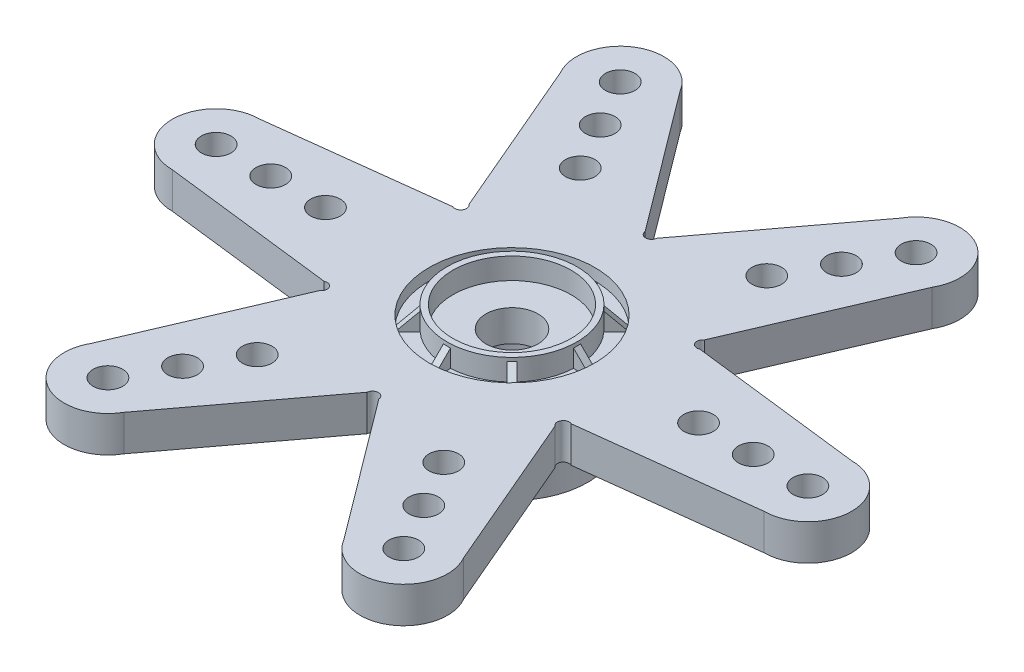
SolidWorks part; units mm, degrees
ref_plane "Front Plane" through (0, 0, 0) normal (0, 0, 1) x (1, 0, 0)
ref_plane "Top Plane" through (0, 0, 0) normal (0, 1, 0) x (1, 0, 0)
ref_plane "Right Plane" through (0, 0, 0) normal (1, 0, 0) x (0, 0, -1)
sketch "Sketch1" plane through (0, 0, 0) normal (0, 1, 0) x (1, 0, 0)
  line L0 (5.7752, -3.8298) -> (0, 0)
  line L1 (6.3503, 3.495) -> (6.3503, 3.8298)
  line L2 (6.3497, -3.4899) -> (15.8747, -2.3469)
  line L3 (6.3503, 3.495) -> (15.8747, 2.3521)
  line L4 (5.7752, 3.8298) -> (0, 0)
  line L5 (6.3503, 3.8298) -> (5.7752, 3.8298)
  line L6 (6.3497, -3.4899) -> (6.3497, -3.8298)
  line L7 (6.3497, -3.8298) -> (5.7752, -3.8298)
  arc A0 (15.8747, -2.3469) -> (15.8747, 2.3521) centre (15.8747, 0.0026) ccw
  dimension "D2" = 4.699
extrude "Extrude4" add sketch "Sketch1" along normal blind 1.9304
sketch "Sketch2" plane through (0, 1.9304, 0) normal (0, 1, 0) x (-1, 0, 0)
  circle A0 centre (-6.3426, -4.1499) radius 0.6604
  circle A1 centre (-6.3426, 4.1499) radius 0.6604
  dimension "D1" = 1.3208
extrude "Cut-Extrude1" cut sketch "Sketch2" against normal through all contours A1 | A0
ref_axis "Axis1" through (0, 0, 0) along (0, 1, 0)
pattern_circular "CirPattern4" count 6 over 360 about axis through (0, 0, 0) along (0, 1, 0) of "Extrude4"
sketch "Sketch3" plane through (0, 1.9304, 0) normal (0, 1, 0) x (-1, 0, 0)
  circle A0 centre (0, 0) radius 1.397
  dimension "D1" = 2.794
extrude "Cut-Extrude2" cut sketch "Sketch3" against normal blind 12.7 and the other way blind 12.7
sketch "Sketch4" plane through (0, 1.9304, 0) normal (0, 1, 0) x (-1, 0, 0)
  circle A0 centre (0, 0) radius 4.445
  dimension "D1" = 8.89
extrude "Cut-Extrude3" cut sketch "Sketch4" against normal blind 0.635
sketch "Sketch5" plane through (0, 1.2954, 0) normal (0, 1, 0) x (-1, 0, 0)
  circle A0 centre (0, 0) radius 3.4925
  circle A1 centre (0, 0) radius 3.175
  dimension "D1" = 6.985
  dimension "D2" = 6.35
extrude "Extrude5" add sketch "Sketch5" along normal blind 1.143 contours A1 | A0
sketch "Sketch8" plane through (0, 0, 0) normal (0, 0, 1) x (1, 0, 0)
  line L1 (4.445, 1.2954) -> (-4.445, 1.2954) construction
  line L4 (-3.4925, 2.2448) -> (-4.443, 1.2954)
rib "Rib10" sketch "Sketch8" sketch "Sketch8" thickness 0.381 extrusion direction parallel to sketch draft on no parameters "D1"=0.381
pattern_circular "CirPattern5" count 8 over 360 about axis through (0, 0, 0) along (0, 1, 0) of "Rib10"
sketch "Sketch9" plane through (0, 1.9304, 0) normal (0, 1, 0) x (-1, 0, 0)
  circle A0 centre (7.9351, 13.7492) radius 0.7937
  arc A1 (9.9698, 12.5744) -> (5.9004, 14.9239) centre (7.9351, 13.7492) ccw construction
  circle A2 centre (6.4692, 11.2092) radius 0.7937
  circle A3 centre (5.0033, 8.6692) radius 0.7937
  dimension "D1" = 1.5875
  dimension "D2" = 2.54
  dimension "D3" = 2.54
extrude "Cut-Extrude4" cut sketch "Sketch9" against normal through all
pattern_circular "CirPattern6" count 6 over 360 about axis through (0, 0, 0) along (0, 1, 0) of "Cut-Extrude4"
sketch "Sketch10" plane through (0, 0, 0) normal (0, -1, 0) x (1, 0, 0)
  circle A0 centre (0, 0) radius 5.08
  dimension "D1" = 10.16
extrude "Extrude6" add sketch "Sketch10" along normal blind 0.762
fillet "Fillet2" radius 0.508 1 edges at (0, 0, 5.08)
sketch "Sketch11" plane through (0, -0.762, 0) normal (0, -1, 0) x (1, 0, 0)
  circle A0 centre (0, 0) radius 4.064
  dimension "D1" = 8.128
extrude "Extrude7" add sketch "Sketch11" along normal blind 3.048
fillet "Fillet3" radius 0.889 1 edges at (0, -0.762, -4.064)
sketch "Sketch12" plane through (0, -3.81, 0) normal (0, -1, 0) x (1, 0, 0)
  circle A0 centre (0, 0) radius 2.8575
  dimension "D1" = 5.715
extrude "Cut-Extrude5" cut sketch "Sketch12" against normal blind 3.429
sketch "Sketch14" plane through (0, -0.381, 0) normal (0, -1, 0) x (1, 0, 0)
  circle A0 centre (0, 0) radius 1.397
  dimension "D1" = 2.794
extrude "Cut-Extrude6" cut sketch "Sketch14" against normal through all
sketch "Sketch15" plane through (0, 1.9304, 0) normal (0, 1, 0) x (-1, 0, 0)
  circle A0 centre (-6.4872, -3.7519) radius 0.3175
  dimension "D1" = 0.635
extrude "Cut-Extrude7" cut sketch "Sketch15" against normal through all and the other way through all
pattern_circular "CirPattern7" count 6 over 360 about axis through (0, 0, 0) along (0, 1, 0) of "Cut-Extrude7"
